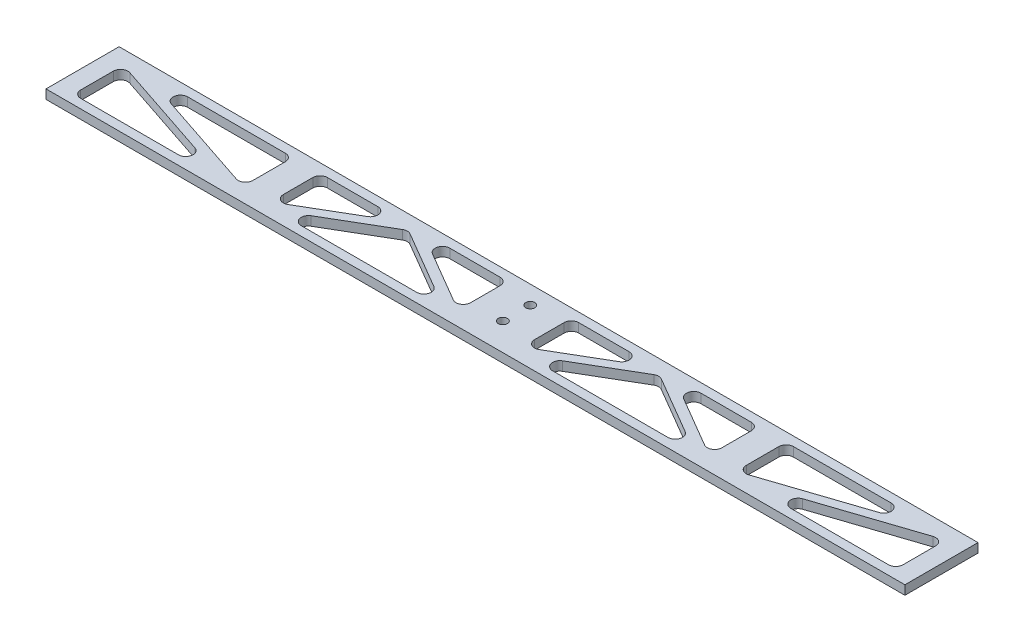
SolidWorks part; units mm, degrees
material "Balsa"
ref_plane "Front Plane" through (0, 0, 0) normal (0, 0, 1) x (1, 0, 0)
ref_plane "Top Plane" through (0, 0, 0) normal (0, 1, 0) x (1, 0, 0)
ref_plane "Right Plane" through (0, 0, 0) normal (1, 0, 0) x (0, 0, -1)
sketch "Sketch1" plane through (0, 0, 0) normal (0, 1, 0) x (1, 0, 0)
  line L1 (149.225, -12.7) -> (-149.225, -12.7)
  line L2 (149.225, -12.7) -> (149.225, 12.7)
  line L3 (149.225, 12.7) -> (-149.225, 12.7)
  line L4 (-149.225, -12.7) -> (-149.225, 12.7)
  point P0 (0, 12.7)
  point P6 (-149.225, 0)
  dimension "D1" = 25.4
  dimension "D2" = 298.45
extrude "Boss-Extrude1" add sketch "Sketch1" along normal blind 3.175
sketch "Sketch2" plane through (0, 3.175, 0) normal (0, 1, 0) x (1, 0, 0)
  line L0 (149.225, -12.7) -> (149.225, 12.7) construction
  line L2 (-149.225, 12.7) -> (-149.225, -12.7) construction
  line L4 (149.225, -12.7) -> (149.225, 12.7)
  line L6 (-149.225, 12.7) -> (-149.225, -12.7)
  line L8 (149.225, 9.525) -> (-149.225, 9.525)
  line L9 (-149.225, -9.525) -> (149.225, -9.525)
  line L10 (-142.875, 9.525) -> (-142.875, -9.525)
  line L11 (-80.9625, 9.525) -> (-80.9625, -9.525) construction
  line L12 (142.875, 9.525) -> (142.875, -9.525)
  line L13 (0, -9.525) -> (0, 9.525) construction
  line L14 (11.1125, 9.525) -> (11.1125, -9.525)
  line L15 (-11.1125, 9.525) -> (-11.1125, -9.525)
  line L16 (-85.725, 9.525) -> (-85.725, -9.525)
  line L17 (-76.2, 9.525) -> (-76.2, -9.525)
  line L18 (80.9625, 9.525) -> (80.9625, -9.525) construction
  line L19 (85.725, 9.525) -> (85.725, -9.525)
  line L20 (76.2, 9.525) -> (76.2, -9.525)
  line L21 (-76.2, -9.525) -> (-43.6562, 9.525)
  line L22 (-43.6562, 9.525) -> (-11.1125, -9.525)
  line L23 (-85.725, -9.525) -> (-142.875, 9.525)
  line L24 (11.1125, -9.525) -> (43.6562, 9.525)
  line L25 (43.6562, 9.525) -> (76.2, -9.525)
  line L26 (85.725, -9.525) -> (142.875, 9.525)
  line L27 (-85.223, -8.019) -> (-142.373, 11.031)
  line L28 (-75.398, -10.895) -> (-43.6562, 7.6855)
  line L29 (-43.6562, 7.6855) -> (-11.9145, -10.895)
  line L30 (11.9145, -10.895) -> (43.6562, 7.6855)
  line L31 (43.6562, 7.6855) -> (75.398, -10.895)
  line L32 (86.227, -11.031) -> (143.377, 8.019)
  line L33 (-86.227, -11.031) -> (-143.377, 8.019)
  line L34 (-77.002, -8.155) -> (-43.6562, 11.3645)
  line L35 (-43.6562, 11.3645) -> (-10.3105, -8.155)
  line L36 (10.3105, -8.155) -> (43.6562, 11.3645)
  line L37 (43.6562, 11.3645) -> (77.002, -8.155)
  line L38 (85.223, -8.019) -> (142.373, 11.031)
  dimension "D1" = 3.175
  dimension "D2" = 3.175
  dimension "D3" = 6.35
  dimension "D4" = 6.35
  dimension "D11" = 4.7625
  dimension "D12" = 4.7625
  dimension "D8" = 9.525
  dimension "D9" = 4.7625
  dimension "D7" = 63.5
  dimension "D10" = 63.5
  dimension "D5" = 22.225
  dimension "D6" = 11.1125
  dimension "D13" = 1.5875
  dimension "D14" = 1.5875
extrude "Cut-Extrude1" cut sketch "Sketch2" against normal through all contours L9 L33 L10 | L27 L16 L8 | L17 L34 L8 | L29 L28 L9 | L8 L35 L15 | L14 L36 L8 | L31 L30 L9 | L8 L37 L20 | L19 L38 L8 | L32 L9 L12 region at (125.4984, 3.175, 3.7328) region at (103.1016, 3.175, -3.7328) region at (66.3996, 3.175, -3.7882) region at (43.6562, 3.175, 3.7882) region at (20.9129, 3.175, -3.7882) region at (-20.9129, 3.175, -3.7882) region at (-43.6562, 3.175, 3.7882) region at (-66.3996, 3.175, -3.7882) region at (-103.1016, 3.175, -3.7328) region at (-125.4984, 3.175, 3.7328)
sketch "Sketch3" plane through (0, 3.175, 0) normal (0, 1, 0) x (1, 0, 0)
  circle A0 centre (0, 6.35) radius 1.5875
  circle A1 centre (0, -3.175) radius 1.5875
  dimension "D1" = 3.175
  dimension "D2" = 9.525
  dimension "D3" = 6.35
extrude "Cut-Extrude2" cut sketch "Sketch3" against normal through all
fillet "Fillet1" radius 2.54 30 edges at (-14.2549, 1.5875, 9.525) (-73.0576, 1.5875, 9.525) (-43.6562, 1.5875, -7.6855) (-11.1125, 1.5875, 7.6855) (-40.5138, 1.5875, -9.525) (-11.1125, 1.5875, -9.525) (-46.7987, 1.5875, -9.525) (-76.2, 1.5875, 7.6855) (-76.2, 1.5875, -9.525) (73.0576, 1.5875, 9.525) (14.2549, 1.5875, 9.525) (43.6562, 1.5875, -7.6855) (142.875, 1.5875, -7.8516) (142.875, 1.5875, 9.525) (90.7451, 1.5875, 9.525) (40.5138, 1.5875, -9.525) (11.1125, 1.5875, 7.6855) (11.1125, 1.5875, -9.525) (76.2, 1.5875, 7.6855) (46.7987, 1.5875, -9.525) (76.2, 1.5875, -9.525) (137.8549, 1.5875, -9.525) (85.725, 1.5875, 7.8516) (85.725, 1.5875, -9.525) (-137.8549, 1.5875, -9.525) (-85.725, 1.5875, 7.8516) (-85.725, 1.5875, -9.525) (-90.7451, 1.5875, 9.525) (-142.875, 1.5875, 9.525) (-142.875, 1.5875, -7.8516)
equation "\"D10@Sketch2\"=\"D7@Sketch2\""
equation "\"D6@Sketch2\"=\"D5@Sketch2\"/2"
